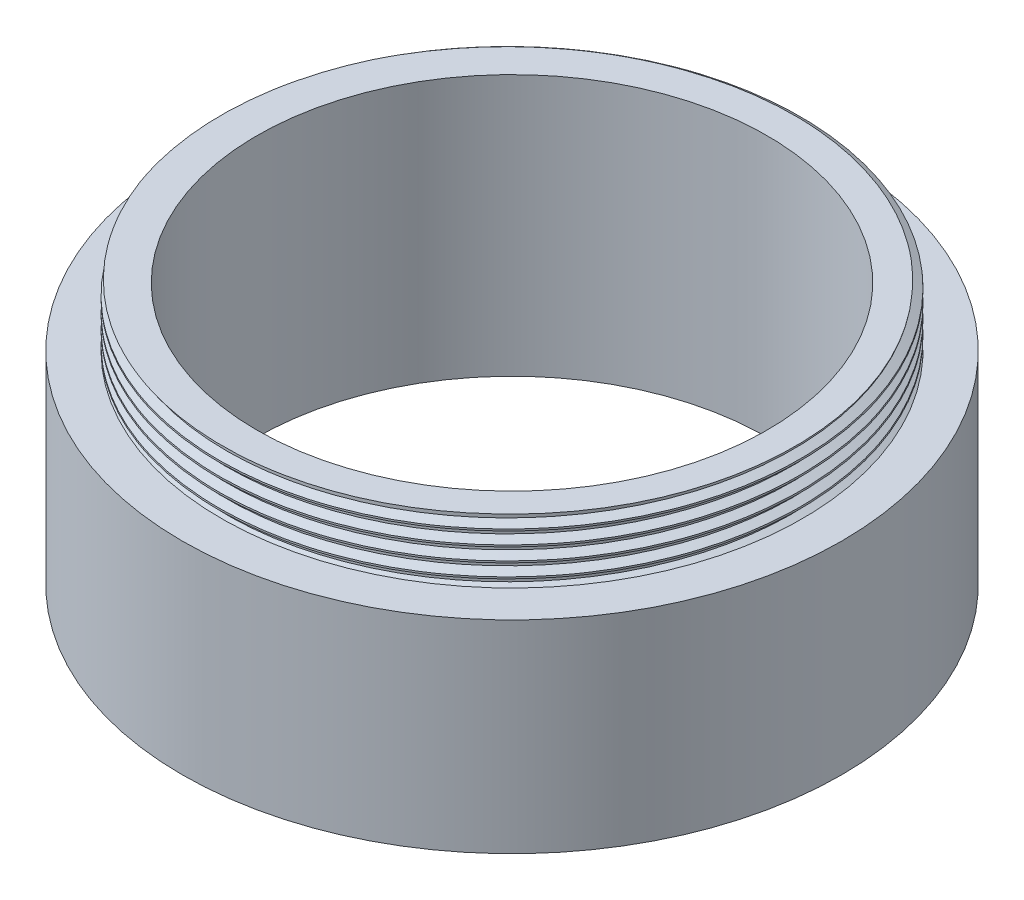
SolidWorks part; units mm, degrees
ref_plane "Front Plane" through (0, 0, 0) normal (0, 0, 1) x (1, 0, 0)
ref_plane "Top Plane" through (0, 0, 0) normal (0, 1, 0) x (1, 0, 0)
ref_plane "Right Plane" through (0, 0, 0) normal (1, 0, 0) x (0, 0, -1)
sketch "Sketch1" plane through (0, 0, 0) normal (0, 1, 0) x (1, 0, 0)
  circle A0 centre (0, 0) radius 44.5
  circle A1 centre (0, 0) radius 39.06
  dimension "D1" = 89
  dimension "D2" = 78.12
extrude "Boss-Extrude1" add sketch "Sketch1" along normal blind 40
thread "Thread1" pitch 2.1167 start angle 0, offset 2, length 12.5, pitch 2.1167, diameter 89
ref_plane "Plane1" through (-44.5, 42, 0) normal (0, 0, 1) x (-1, 0, 0)
sketch "Thread Profile1" plane through (-44.5, 42, 0) normal (0, 0, 1) x (-1, 0, 0)
  line L0 (0, 0) -> (0, 2.1167) construction
  line L11 (0, 0) -> (0, 1.8521)
  line L12 (0, 1.8521) -> (-1.1457, 1.1906)
  line L13 (-1.1457, 1.1906) -> (-1.1457, 0.6615)
  line L15 (-1.1457, 0.6615) -> (0, 0)
  line L17 (-1.1457, 0.926) -> (0, 0.926) construction
  point P2 (0, 0)
  dimension "Pitch" = 2.1167
  dimension "Profile_Angle" = 60
  dimension "Profile_Land" = 0.5292
  dimension "Profile_Height" = 1.1457
sketch "Sketch2" plane through (0, 0, 0) normal (0, -1, 0) x (1, 0, 0)
  circle A0 centre (0, 0) radius 44.5
  circle A1 centre (0, 0) radius 50.4825
  dimension "D1" = 100.965
extrude "Boss-Extrude2" add sketch "Sketch2" against normal blind 31
